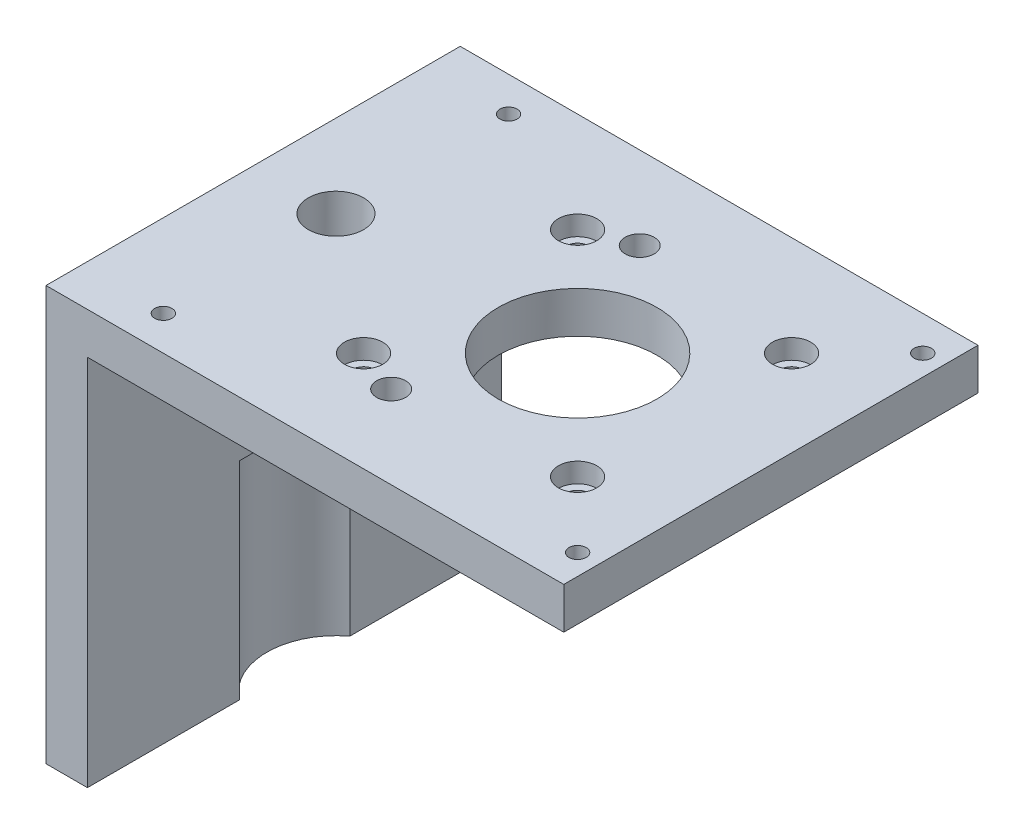
SolidWorks part; units mm, degrees
material "6061 Alloy"
ref_plane "Front Plane" through (0, 0, 0) normal (0, 0, 1) x (1, 0, 0)
ref_plane "Top Plane" through (0, 0, 0) normal (0, 1, 0) x (1, 0, 0)
ref_plane "Right Plane" through (0, 0, 0) normal (1, 0, 0) x (0, 0, -1)
sketch "Sketch1" plane through (0, 0, 0) normal (0, 0, 1) x (1, 0, 0)
  line L0 (0, 0) -> (6, 0)
  line L2 (0, 0) -> (0, 60)
  line L3 (0, 60) -> (75, 60)
  line L4 (75, 54) -> (75, 60)
  line L6 (6, 0) -> (6, 54)
  line L7 (6, 54) -> (75, 54)
  dimension "D1" = 75
  dimension "D2" = 6
  dimension "D3" = 6
  dimension "D4" = 60
extrude "Boss-Extrude1" add sketch "Sketch1" along normal blind 60
sketch "Sketch2" plane through (0, 60, 0) normal (0, 1, 0) x (1, 0, 0)
  line L0 (31.5, -45.5) -> (62.5, -45.5) construction
  line L1 (31.5, -45.5) -> (31.5, -14.5) construction
  line L2 (75, -60) -> (75, 0) construction
  circle A0 centre (47, -30) radius 11.5
  point P2 (31.5, -45.5)
  point P3 (47, -45.5)
  point P4 (31.5, -30)
  point P5 (62.5, -45.5)
  point P6 (31.5, -14.5)
  point P7 (62.5, -14.5)
  dimension "D1" = 23
  dimension "D2" = 31
  dimension "D3" = 31
  dimension "D6" = 28
  dimension "D4" = 2
  dimension "D5" = 2
extrude "Cut-Extrude1" cut sketch "Sketch2" against normal through all
ref_axis "Axis1" through (47, 54, 30) along (0, 1, 0)
hole_wizard "CBORE for #4 Socket Head Cap Screw1" positions "Sketch7" profile "Sketch6" counterbore size "#4" standard "Ansi Inch" end condition through all
sketch "Sketch7" plane through (0, 60, 0) normal (0, 1, 0) x (-1, 0, 0)
  line L0 (-31.5, 45.5) -> (-62.5, 45.5) construction
  line L1 (-31.5, 45.5) -> (-31.5, 14.5) construction
  point P0 (-31.5, 45.5)
  point P8 (-62.5, 45.5)
  point P9 (-31.5, 14.5)
  point P10 (-62.5, 14.5)
  point P34 (-47, 45.5)
  point P35 (-31.5, 30)
  dimension "D1" = 31
  dimension "D4" = 31
  dimension "D2" = 2
  dimension "D3" = 2
sketch "Sketch6" plane through (31.5, 60, 45.5) normal (1, 0, 0) x (0, 0, 1)
  line L0 (0, 0) -> (0, 60)
  line L1 (0, 60) -> (1.6319, 60)
  line L3 (1.6319, 60) -> (1.632, 2.8448)
  line L4 (1.632, 2.8448) -> (2.7788, 2.8448)
  line L5 (2.7788, 2.8448) -> (2.7788, 0)
  line L7 (2.7788, 0) -> (0, 0)
  line L11 (0, -6.35) -> (0, 107.95) construction
  dimension "Thru Hole Dia." = 3.2639
  dimension "Thru Hole Depth" = 60
  dimension "C'Bore Dia." = 5.5575
  dimension "C'Bore Depth" = 2.8448
hole_wizard "M3 Tapped Hole1" positions "Sketch9" profile "Sketch10" tap size "M3" standard "ISO"
sketch "Sketch9" plane through (0, 60, 0) normal (0, 1, 0) x (-1, 0, 0)
  line L0 (-12, 55) -> (-72, 55) construction
  line L1 (-12, 55) -> (-12, 5) construction
  line L19 (-75, 60) -> (-75, 0) construction
  line L20 (-75, 60) -> (0, 60) construction
  point P1 (-12, 55)
  point P5 (-72, 55)
  point P6 (-12, 5)
  point P7 (-72, 5)
  dimension "D1" = 60
  dimension "D2" = 50
  dimension "D5" = 3
  dimension "D6" = 5
  dimension "D3" = 2
  dimension "D4" = 2
sketch "Sketch10" plane through (12, 60, 55) normal (1, 0, 0) x (0, 0, 1)
  line L0 (0, 0) -> (0, 9.2511)
  line L1 (0, 9.2511) -> (1.25, 8.5)
  line L2 (1.25, 8.5) -> (1.25, 0)
  line L5 (1.25, 0) -> (0, 0)
  line L10 (0, 9.2511) -> (-1.25, 8.5) construction
  line L11 (0, -6.35) -> (0, 107.95) construction
  dimension "Tap Drill Dia." = 2.5
  dimension "Tap Drill Depth" = 8.5
  dimension "Drill Angle" = 118
cosmetic thread "Hole Thread1" parameters "D1"=6, "D2"=3
cosmetic thread "Hole Thread2" parameters "D1"=6, "D2"=3
cosmetic thread "Hole Thread3" parameters "D1"=6, "D2"=3
cosmetic thread "Hole Thread4" parameters "D1"=6, "D2"=3
hole_wizard "M5 Tapped Hole1" positions "Sketch14" profile "Sketch15" tap size "M5" standard "ISO" end condition through all
sketch "Sketch14" plane through (0, 60, 0) normal (0, 1, 0) x (-1, 0, 0)
  line L0 (-38, 12) -> (-38, 48) construction
  point P0 (-38, 12)
  point P1 (-38, 48)
  dimension "D1" = 18
  dimension "D2" = 18
  dimension "D3" = 9
sketch "Sketch15" plane through (38, 60, 12) normal (1, 0, 0) x (0, 0, 1)
  line L0 (0, 0) -> (0, 60)
  line L1 (0, 60) -> (2.1, 60)
  line L2 (2.1, 60) -> (2.1, 0)
  line L5 (2.1, 0) -> (0, 0)
  line L11 (0, -6.35) -> (0, 107.95) construction
  dimension "Thru Tap Drill Dia." = 4.2
  dimension "Thru Tap Drill Depth" = 60
cosmetic thread "Hole Thread5" parameters "D2"=5
cosmetic thread "Hole Thread6" parameters "D2"=5
sketch "Sketch11" plane through (0, 60, 0) normal (0, 1, 0) x (1, 0, 0)
  line L1 (0, -60) -> (0, 0) construction
  line L2 (75, -30) -> (0, -30) construction
  line L3 (75, -60) -> (75, 0) construction
  circle A0 centre (12, -30) radius 4
  dimension "D2" = 8
  dimension "D1" = 12
extrude "Cut-Extrude2" cut sketch "Sketch11" against normal through all
sketch "Sketch16" plane through (0, 0, 0) normal (0, -1, 0) x (1, 0, 0)
  circle A0 centre (12, 30) radius 10
extrude "Cut-Extrude4" cut sketch "Sketch16" against normal blind 30
